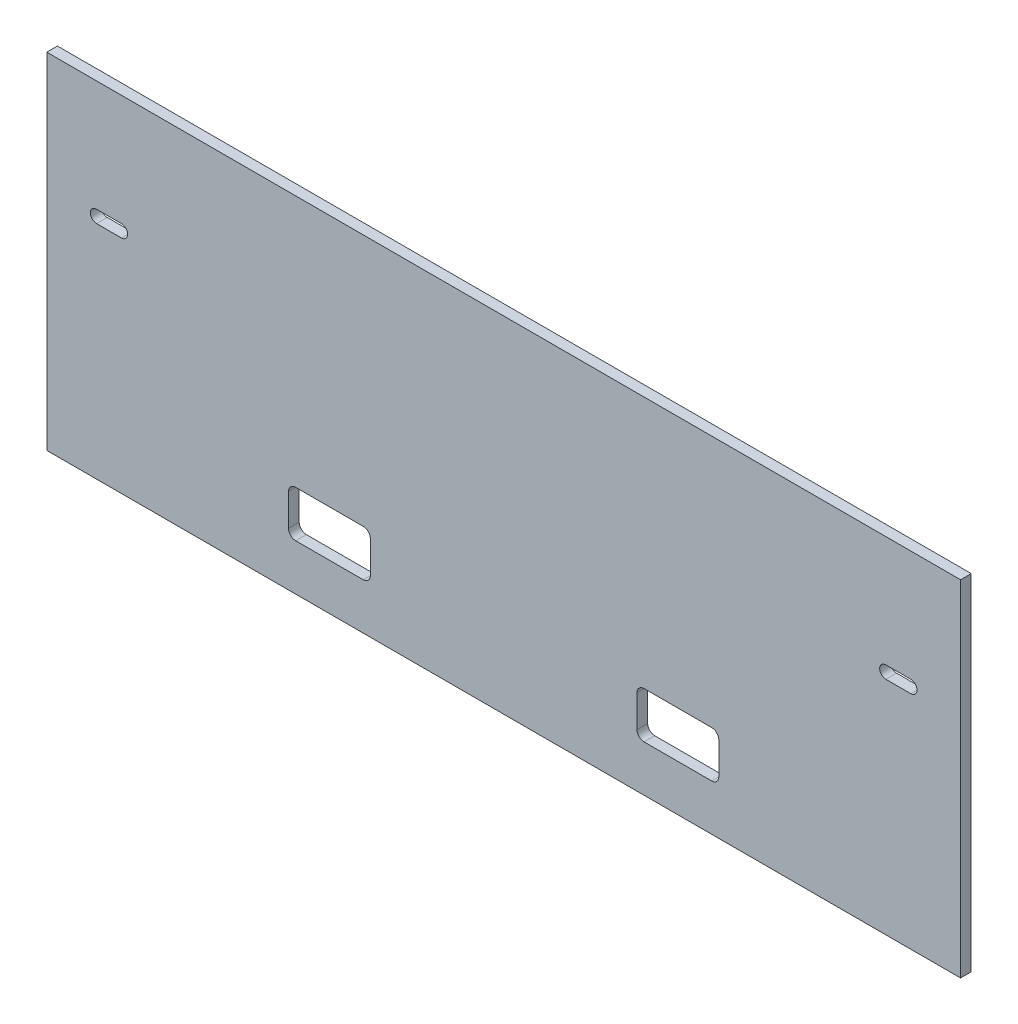
SolidWorks part; units mm, degrees
ref_plane "Plan de face" through (0, 0, 0) normal (0, 0, 1) x (1, 0, 0)
ref_plane "Plan de dessus" through (0, 0, 0) normal (0, 1, 0) x (1, 0, 0)
ref_plane "Plan de droite" through (0, 0, 0) normal (1, 0, 0) x (0, 0, -1)
sketch "Esquisse1" plane through (0, 0, 0) normal (0, 0, 1) x (1, 0, 0)
  line L0 (0, 48.5) -> (0, -48.5) construction
  line L1 (128.5, 48.5) -> (-128.5, 48.5)
  line L2 (128.5, 48.5) -> (128.5, -48.5)
  line L3 (128.5, -48.5) -> (-128.5, -48.5)
  line L4 (-128.5, 48.5) -> (-128.5, -48.5)
  line L5 (128.5, 48.5) -> (-128.5, -48.5) construction
  line L6 (128.5, -48.5) -> (-128.5, 48.5) construction
  line L7 (-111, 15.5) -> (0, 15.5) construction
  line L8 (-114.5, 15.5) -> (-107.5, 15.5) construction
  line L9 (-114.5, 17.25) -> (-107.5, 17.25)
  line L10 (-114.5, 13.75) -> (-107.5, 13.75)
  line L11 (107.5, 15.5) -> (114.5, 15.5) construction
  line L12 (107.5, 17.25) -> (114.5, 17.25)
  line L13 (107.5, 13.75) -> (114.5, 13.75)
  circle A0 centre (-111, 15.5) radius 1.75 construction
  circle A1 centre (111, 15.5) radius 1.75 construction
  arc A2 (-114.5, 17.25) -> (-114.5, 13.75) centre (-114.5, 15.5) ccw
  arc A3 (-107.5, 13.75) -> (-107.5, 17.25) centre (-107.5, 15.5) ccw
  arc A4 (107.5, 17.25) -> (107.5, 13.75) centre (107.5, 15.5) ccw
  arc A5 (114.5, 13.75) -> (114.5, 17.25) centre (114.5, 15.5) ccw
  point P0 (0, 0)
  point P15 (-111, 15.5)
  point P22 (111, 15.5)
  point P27 (0, 0)
  point P28 (0, 0)
  dimension "D3" = 3.5
  dimension "D7" = 1.75
  dimension "D9" = 1.75
  dimension "D1" = 257
  dimension "D2" = 97
  dimension "D4" = 111
  dimension "D5" = 33
  dimension "D6" = 7
  dimension "D8" = 7
extrude "Boss.-Extru.1" add sketch "Esquisse1" along normal blind 3
sketch "Esquisse2" plane through (0, 0, 3) normal (0, 0, 1) x (1, 0, 0)
  line L0 (-37.5, -35.5) -> (37.5, -35.5) construction
  line L1 (-60.5, -35.5) -> (-37.5, -35.5)
  line L2 (-60.5, -35.5) -> (-60.5, -22.5)
  line L3 (-60.5, -22.5) -> (-37.5, -22.5)
  line L4 (-37.5, -35.5) -> (-37.5, -22.5)
  line L5 (37.5, -35.5) -> (60.5, -35.5)
  line L6 (37.5, -35.5) -> (37.5, -22.5)
  line L7 (37.5, -22.5) -> (60.5, -22.5)
  line L8 (60.5, -35.5) -> (60.5, -22.5)
  line L9 (0, 0) -> (0, -35.5) construction
  line L10 (-128.5, -48.5) -> (128.5, -48.5) construction
  point P8 (-49, -22.5)
  point P9 (49, -22.5)
  dimension "D1" = 98
  dimension "D2" = 23
  dimension "D3" = 13
  dimension "D4" = 13
extrude "Enlèv. mat.-Extru.1" cut sketch "Esquisse2" against normal up to next
fillet "Congé1" radius 2 8 edges at (37.5, -35.5, 1.5) (60.5, -35.5, 1.5) (60.5, -22.5, 1.5) (37.5, -22.5, 1.5) (-60.5, -35.5, 1.5) (-37.5, -35.5, 1.5) (-37.5, -22.5, 1.5) (-60.5, -22.5, 1.5)
